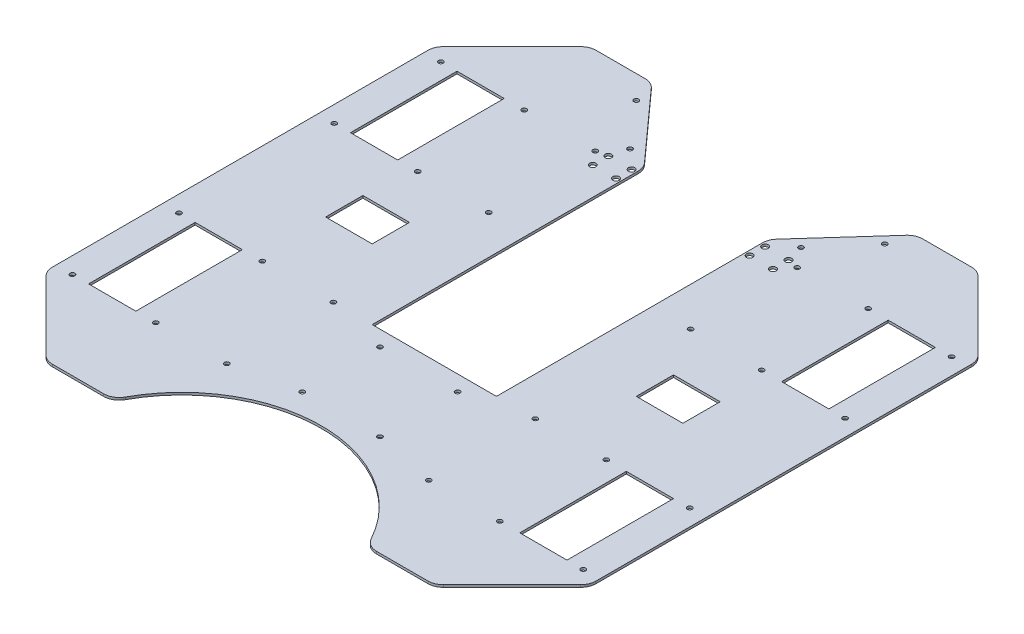
SolidWorks part; units mm, degrees
material "PMMA"
ref_plane "前视基准面" through (0, 0, 0) normal (0, 0, 1) x (1, 0, 0)
ref_plane "上视基准面" through (0, 0, 0) normal (0, 1, 0) x (1, 0, 0)
ref_plane "右视基准面" through (0, 0, 0) normal (1, 0, 0) x (0, 0, -1)
other "Configuration Table"
sketch "草图1" plane through (0, 0, 0) normal (0, 1, 0) x (1, 0, 0)
  line L0 (-125, 175) -> (-175, 125)
  line L1 (125, -175) -> (81.7103, -175)
  line L2 (175, -125) -> (175, 125)
  line L3 (125, 175) -> (85, 175)
  line L4 (-175, -125) -> (-175, 125)
  line L5 (-85, 175) -> (-40, 125)
  line L7 (125, 175) -> (175, 125)
  line L8 (175, -125) -> (125, -175)
  line L9 (-125, -175) -> (-175, -125)
  line L10 (40, 125) -> (85, 175)
  line L11 (-85, 175) -> (-125, 175)
  line L12 (40, 125) -> (40, 85)
  line L13 (40, 85) -> (-40, 85)
  line L14 (-40, 85) -> (-40, 125)
  line L15 (-153.994, 50) -> (-123.594, 50)
  line L16 (-123.594, 50) -> (-123.594, 118.58)
  line L17 (-123.594, 118.58) -> (-153.994, 118.58)
  line L18 (-153.994, 118.58) -> (-153.994, 50)
  line L19 (123.594, 50) -> (153.994, 50)
  line L20 (153.994, 50) -> (153.994, 118.58)
  line L21 (153.994, 118.58) -> (123.594, 118.58)
  line L22 (123.594, 118.58) -> (123.594, 50)
  line L23 (-175, 0) -> (175, 0) construction
  line L24 (-123.594, -118.58) -> (-153.994, -118.58)
  line L25 (-123.594, -50) -> (-123.594, -118.58)
  line L26 (-153.994, -50) -> (-123.594, -50)
  line L27 (-153.994, -118.58) -> (-153.994, -50)
  line L28 (153.994, -118.58) -> (123.594, -118.58)
  line L29 (153.994, -50) -> (153.994, -118.58)
  line L30 (123.594, -50) -> (153.994, -50)
  line L31 (123.594, -118.58) -> (123.594, -50)
  line L32 (-81.7103, -175) -> (-125, -175)
  line L33 (-80, 160) -> (-55, 131) construction
  line L34 (0, 85) -> (0, -124.4881) construction
  line L35 (-40, 85) -> (-40, -25)
  line L36 (-40, -25) -> (40, -25)
  line L37 (40, -25) -> (40, 85)
  circle A0 centre (-55, 131) radius 1.55
  circle A1 centre (-80, 160) radius 1.55
  circle A2 centre (55, 131) radius 1.55
  circle A3 centre (80, 160) radius 1.55
  circle A4 centre (-65, 118.58) radius 1.55
  circle A5 centre (-65, 50) radius 1.55
  circle A6 centre (-110.72, 50) radius 1.55
  circle A7 centre (-110.72, 118.58) radius 1.55
  circle A12 centre (-164.434, 118.58) radius 1.55
  circle A13 centre (-164.434, 50) radius 1.55
  circle A14 centre (-65, -118.58) radius 1.55
  circle A15 centre (-65, -50) radius 1.55
  circle A16 centre (-110.72, -50) radius 1.55
  circle A17 centre (-110.72, -118.58) radius 1.55
  circle A18 centre (-164.434, -50) radius 1.55
  circle A19 centre (-164.434, -118.58) radius 1.55
  circle A20 centre (65, 50) radius 1.55
  circle A21 centre (110.72, 50) radius 1.55
  circle A22 centre (110.72, 118.58) radius 1.55
  circle A23 centre (65, 118.58) radius 1.55
  circle A24 centre (164.434, 118.58) radius 1.55
  circle A25 centre (164.434, 50) radius 1.55
  circle A26 centre (164.434, -118.58) radius 1.55
  circle A27 centre (164.434, -50) radius 1.55
  circle A28 centre (110.72, -50) radius 1.55
  circle A29 centre (110.72, -118.58) radius 1.55
  circle A30 centre (65, -118.58) radius 1.55
  circle A31 centre (65, -50) radius 1.55
  arc A32 (-81.7103, -175) -> (81.7103, -175) centre (0, -212.7283) cw
  circle A33 centre (25, -60) radius 1.55
  circle A34 centre (25, -110) radius 1.55
  circle A35 centre (-25, -60) radius 1.55
  circle A36 centre (-25, -110) radius 1.55
  circle A37 centre (-43, 120) radius 2.05
  circle A38 centre (-43, 110) radius 2.05
  circle A39 centre (-58, 110) radius 2.05
  circle A40 centre (-58, 120) radius 2.05
  circle A41 centre (43, 120) radius 2.05
  circle A42 centre (58, 120) radius 2.05
  circle A43 centre (58, 110) radius 2.05
  circle A44 centre (43, 110) radius 2.05
  point P0 (0, 0)
  point P1 (-85, 175)
  point P2 (85, 175)
  point P3 (40, 125)
  point P4 (-40, 125)
  point P6 (125, 175)
  point P8 (175, 125)
  point P10 (175, -125)
  point P11 (125, -175)
  point P12 (-125, -175)
  point P13 (-175, -125)
  point P24 (-80, 160)
  point P25 (-55, 131)
  point P26 (55, 131)
  point P27 (80, 160)
  point P36 (-164.434, 118.58)
  point P37 (-164.434, 50)
  point P38 (-153.994, 118.58)
  point P39 (-123.594, 50)
  point P40 (-110.72, 118.58)
  point P41 (-110.72, 50)
  point P42 (-65, 118.58)
  point P43 (-65, 50)
  point P47 (-123.594, 118.58)
  point P53 (-153.994, 50)
  point P66 (-40, 85)
  point P67 (40, 85)
  point P70 (110.72, 50)
  point P71 (65, 50)
  point P72 (123.594, 50)
  point P73 (153.994, 50)
  point P74 (164.434, 50)
  point P75 (65, 118.58)
  point P76 (110.72, 118.58)
  point P77 (123.594, 118.58)
  point P78 (153.994, 118.58)
  point P81 (164.434, 118.58)
  point P85 (-65, -118.58)
  point P88 (-65, -50)
  point P91 (-110.72, -50)
  point P94 (-110.72, -118.58)
  point P101 (-164.434, -50)
  point P104 (-164.434, -118.58)
  point P118 (164.434, -118.58)
  point P121 (164.434, -50)
  point P128 (110.72, -50)
  point P131 (110.72, -118.58)
  point P134 (65, -118.58)
  point P137 (65, -50)
  point P157 (58, 110)
  point P158 (43, 110)
  point P159 (43, 120)
  point P160 (58, 120)
  dimension "D29" = 3.1
  dimension "D30" = 3.1
  dimension "D31" = 3.1
  dimension "D32" = 3.1
  dimension "D40" = 3.1
  dimension "D41" = 3.1
  dimension "D42" = 3.1
  dimension "D43" = 3.1
  dimension "D44" = 3.1
  dimension "D45" = 3.1
  dimension "D46" = 3.1
  dimension "D47" = 3.1
  dimension "D48" = 3.1
  dimension "D49" = 3.1
  dimension "D60" = 3.1
  dimension "D61" = 3.1
  dimension "D62" = 43.2897
  dimension "D63" = 90
  dimension "D67" = 3.1
  dimension "D68" = 3.1
  dimension "D69" = 3.1
  dimension "D70" = 3.1
  dimension "D75" = 4.1
  dimension "D76" = 4.1
  dimension "D77" = 4.1
  dimension "D78" = 4.1
  dimension "D80" = 110
  dimension "D1" = 175
  dimension "D2" = 175
  dimension "D3" = 125
  dimension "D4" = 125
  dimension "D5" = 125
  dimension "D6" = 125
  dimension "D7" = 125
  dimension "D8" = 125
  dimension "D9" = 125
  dimension "D10" = 125
  dimension "D11" = 175
  dimension "D12" = 175
  dimension "D13" = 40
  dimension "D14" = 40
  dimension "D15" = 85
  dimension "D16" = 85
  dimension "D17" = 125
  dimension "D18" = 125
  dimension "D19" = 40
  dimension "D20" = 45
  dimension "D21" = 160
  dimension "D22" = 160
  dimension "D23" = 80
  dimension "D24" = 80
  dimension "D25" = 55
  dimension "D26" = 131
  dimension "D27" = 55
  dimension "D28" = 131
  dimension "D33" = 50
  dimension "D34" = 118.58
  dimension "D35" = 65
  dimension "D36" = 45.72
  dimension "D37" = 12.874
  dimension "D38" = 30.4
  dimension "D39" = 10.44
  dimension "D50" = 40
  dimension "D51" = 40
  dimension "D52" = 85
  dimension "D53" = 85
  dimension "D54" = 138.013
  dimension "D55" = 65
  dimension "D56" = 45.72
  dimension "D57" = 12.874
  dimension "D58" = 30.4
  dimension "D59" = 10.44
  dimension "D64" = 0
  dimension "D65" = 25
  dimension "D66" = 25
  dimension "D71" = 60
  dimension "D72" = 50
  dimension "D73" = 15
  dimension "D74" = 10
  dimension "D79" = 43
  dimension "D81" = 120
  dimension "D82" = 110
extrude "凸台-拉伸1" add sketch "草图1" along normal blind 1.5 contours A1 | A0 | L8 L1 A32 L32 L9 L4 L0 L11 L5 L14 L13 L12 L10 L3 L7 L2 | A5 | A3 | A2 | A4 | A7 | A12 | L16 L17 L18 L15 | A6 | L21 L22 L19 L20 | A13 | A16 | A17 | A14 | A15 | A18 | A19 | L25 L24 L27 L26 | A20 | A21 | A22 | A23 | A24 | A25 | A28 | A26 | A27 | L28 L31 L30 L29 | A30 | A31 | A29 | A35 | A36 | A33 | A34 | A39 | A40 | A37 | A38 | A43 | A42 | A41 | A44
fillet "圆角1" radius 10 1 edges at (-40, 0.75, -125)
fillet "圆角2" radius 10 1 edges at (40, 0.75, -125)
fillet "圆角3" radius 10 12 edges at (-85, 0.75, -175) (85, 0.75, -175) (125, 0.75, -175) (175, 0.75, -125) (175, 0.75, 125) (125, 0.75, 175) (81.7103, 0.75, 175) (-81.7103, 0.75, 175) (-125, 0.75, 175) (-175, 0.75, 125) (-175, 0.75, -125) (-125, 0.75, -175)
sketch "草图2" plane through (0, 1.5, 0) normal (0, 1, 0) x (1, 0, 0)
  line L1 (-40, 85) -> (40, 85)
  line L2 (-40, 85) -> (-40, -50)
  line L3 (-40, -50) -> (40, -50)
  line L4 (40, 85) -> (40, -50)
  dimension "D1" = 80
  dimension "D2" = 135
extrude "切除-拉伸1" cut sketch "草图2" against normal blind 10
sketch "草图3" plane through (0, 1.5, 0) normal (0, 1, 0) x (1, 0, 0)
  line L0 (-87.875, -175) -> (-120.8579, -175) construction
  line L1 (-115, 19) -> (-85, 19)
  line L2 (-115, 19) -> (-115, -5)
  line L3 (-115, -5) -> (-85, -5)
  line L4 (-85, 19) -> (-85, -5)
  line L5 (-175, -120.8579) -> (-175, 120.8579) construction
  line L6 (120.8579, -175) -> (87.875, -175) construction
  line L7 (85, 19) -> (115, 19)
  line L8 (85, 19) -> (85, -5)
  line L9 (85, -5) -> (115, -5)
  line L10 (115, 19) -> (115, -5)
  line L11 (175, -120.8579) -> (175, 120.8579) construction
  dimension "D1" = 30
  dimension "D2" = 24
  dimension "D3" = 170
  dimension "D4" = 60
  dimension "D5" = 30
  dimension "D6" = 24
  dimension "D7" = 170
  dimension "D8" = 60
extrude "切除-拉伸2" cut sketch "草图3" against normal blind 10
